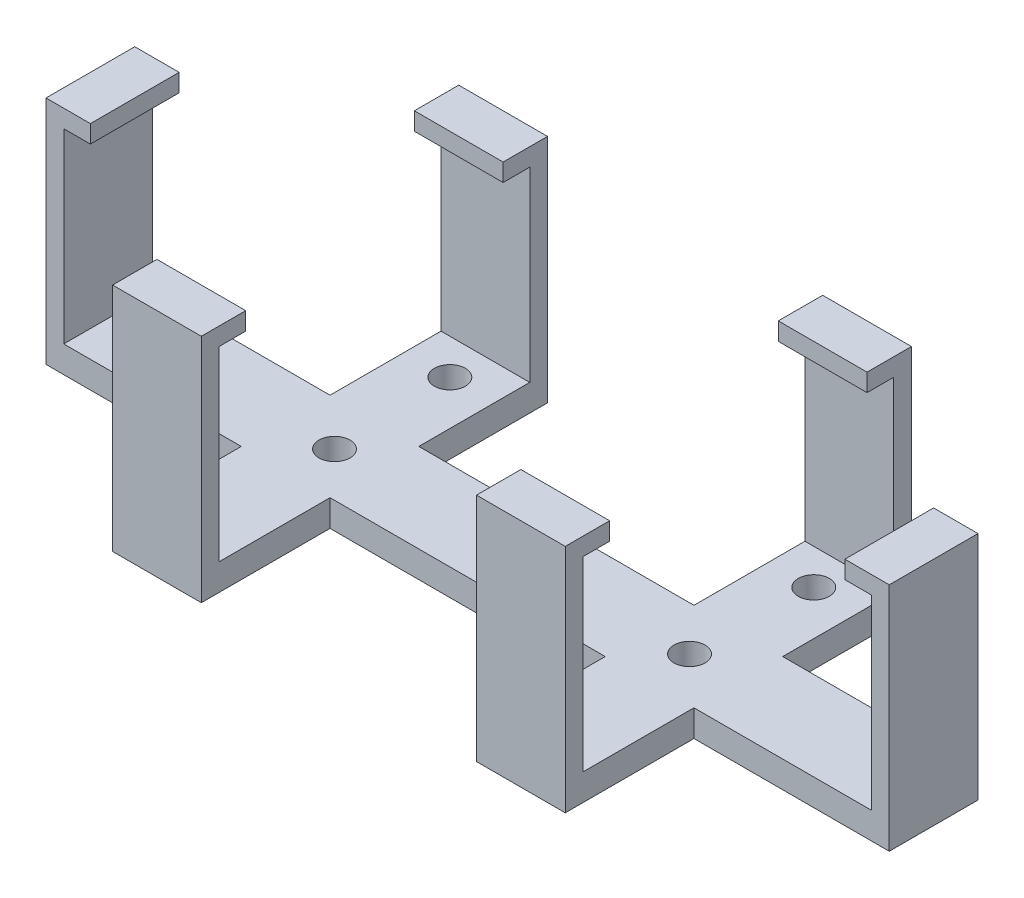
SolidWorks part; units mm, degrees
ref_plane "Front Plane" through (0, 0, 0) normal (0, 0, 1) x (1, 0, 0)
ref_plane "Top Plane" through (0, 0, 0) normal (0, 1, 0) x (1, 0, 0)
ref_plane "Right Plane" through (0, 0, 0) normal (1, 0, 0) x (0, 0, -1)
sketch "Sketch1" plane through (0, 0, 0) normal (0, 1, 0) x (1, 0, 0)
  line L1 (-35.1429, 16.9286) -> (55.8571, 16.9286)
  line L2 (-35.1429, 16.9286) -> (-35.1429, 6.9286)
  line L3 (-35.1429, 6.9286) -> (55.8571, 6.9286)
  line L4 (55.8571, 16.9286) -> (55.8571, 6.9286)
  line L5 (-15.1429, 16.9286) -> (-5.1429, 16.9286)
  line L6 (-15.1429, 16.9286) -> (-15.1429, 29.4286)
  line L7 (-15.1429, 29.4286) -> (-5.1429, 29.4286)
  line L8 (-5.1429, 16.9286) -> (-5.1429, 29.4286)
  line L9 (25.8571, 16.9286) -> (35.8571, 16.9286)
  line L10 (25.8571, 16.9286) -> (25.8571, 29.4286)
  line L11 (25.8571, 29.4286) -> (35.8571, 29.4286)
  line L12 (35.8571, 16.9286) -> (35.8571, 29.4286)
  line L13 (-15.1429, 6.9286) -> (-5.1429, 6.9286)
  line L14 (-15.1429, 6.9286) -> (-15.1429, -5.5714)
  line L15 (-15.1429, -5.5714) -> (-5.1429, -5.5714)
  line L16 (-5.1429, 6.9286) -> (-5.1429, -5.5714)
  line L17 (25.8571, 6.9286) -> (35.8571, 6.9286)
  line L18 (25.8571, 6.9286) -> (25.8571, -5.5714)
  line L19 (25.8571, -5.5714) -> (35.8571, -5.5714)
  line L20 (35.8571, 6.9286) -> (35.8571, -5.5714)
  line L21 (25.8571, 29.4286) -> (35.8571, 29.4286)
  line L22 (25.8571, 29.4286) -> (25.8571, 31.4286)
  line L23 (25.8571, 31.4286) -> (35.8571, 31.4286)
  line L24 (35.8571, 29.4286) -> (35.8571, 31.4286)
  line L25 (-15.1429, 29.4286) -> (-5.1429, 29.4286)
  line L26 (-15.1429, 29.4286) -> (-15.1429, 31.4286)
  line L27 (-15.1429, 31.4286) -> (-5.1429, 31.4286)
  line L28 (-5.1429, 29.4286) -> (-5.1429, 31.4286)
  line L29 (-15.1429, -5.5714) -> (-5.1429, -5.5714)
  line L30 (-15.1429, -5.5714) -> (-15.1429, -7.5714)
  line L31 (-15.1429, -7.5714) -> (-5.1429, -7.5714)
  line L32 (-5.1429, -5.5714) -> (-5.1429, -7.5714)
  line L33 (25.8571, -5.5714) -> (35.8571, -5.5714)
  line L34 (25.8571, -5.5714) -> (25.8571, -7.5714)
  line L35 (25.8571, -7.5714) -> (35.8571, -7.5714)
  line L36 (35.8571, -5.5714) -> (35.8571, -7.5714)
  line L37 (55.8571, 16.9286) -> (57.8571, 16.9286)
  line L38 (55.8571, 16.9286) -> (55.8571, 6.9286)
  line L39 (55.8571, 6.9286) -> (57.8571, 6.9286)
  line L40 (57.8571, 16.9286) -> (57.8571, 6.9286)
  line L41 (-35.1429, 16.9286) -> (-37.1429, 16.9286)
  line L42 (-35.1429, 16.9286) -> (-35.1429, 6.9286)
  line L43 (-35.1429, 6.9286) -> (-37.1429, 6.9286)
  line L44 (-37.1429, 16.9286) -> (-37.1429, 6.9286)
  circle A0 centre (-9.6429, 11.9286) radius 1.75
  circle A1 centre (30.3571, 11.9286) radius 1.75
  point P32 (-35.1429, 11.9286)
  point P33 (55.8571, 11.9286)
  dimension "D23" = 3.5
  dimension "D24" = 3.5
  dimension "D1" = 91
  dimension "D2" = 10
  dimension "D3" = 10
  dimension "D4" = 10
  dimension "D5" = 20
  dimension "D6" = 20
  dimension "D7" = 20
  dimension "D8" = 20
  dimension "D9" = 10
  dimension "D10" = 10
  dimension "D11" = 12.5
  dimension "D12" = 2
  dimension "D13" = 12.5
  dimension "D14" = 2
  dimension "D15" = 12.5
  dimension "D16" = 12.5
  dimension "D17" = 2
  dimension "D18" = 2
  dimension "D19" = 0
  dimension "D20" = 0
  dimension "D21" = 40
  dimension "D22" = 25.5
  dimension "D25" = 2
  dimension "D26" = 2
extrude "Boss-Extrude1" add sketch "Sketch1" along normal blind 3 contours L1 L8 L7 L6 | L4 L1 L2 L3 A1 A0 | L16 L3 L14 L15 | L20 L3 L18 L19 | L1 L12 L11 L10 region at (10.3571, 0, -11.9286) region at (-10.1429, 0, -23.1786) region at (-10.1429, 0, -0.6786) region at (30.8571, 0, -23.1786) region at (30.8571, 0, -0.6786)
extrude "Boss-Extrude2" add sketch "Sketch1<3>" along normal blind 24 contours L41 L44 L43 L2 | L32 L15 L30 L31 | L36 L19 L34 L35 | L40 L37 L4 L39 | L11 L24 L23 L22 | L7 L28 L27 L26 region at (-36.1429, 0, -11.9286) region at (-10.1429, 0, -30.4286) region at (-10.1429, 0, 6.5714) region at (30.8571, 0, -30.4286) region at (56.8571, 0, -11.9286) region at (30.8571, 0, 6.5714)
sketch "Sketch1<3>" plane through (0, 0, 0) normal (0, 1, 0) x (1, 0, 0) same geometry as "Sketch1"
sketch "Sketch2" plane through (0, 24, 0) normal (0, 1, 0) x (1, 0, 0)
  line L1 (-15.1429, 31.4286) -> (-5.1429, 31.4286)
  line L2 (-15.1429, 31.4286) -> (-15.1429, 26.4286)
  line L3 (-15.1429, 26.4286) -> (-5.1429, 26.4286)
  line L4 (-5.1429, 31.4286) -> (-5.1429, 26.4286)
  line L5 (25.8571, 31.4286) -> (35.8571, 31.4286)
  line L6 (25.8571, 31.4286) -> (25.8571, 26.4286)
  line L7 (25.8571, 26.4286) -> (35.8571, 26.4286)
  line L8 (35.8571, 31.4286) -> (35.8571, 26.4286)
  line L9 (57.8571, 16.9286) -> (52.8571, 16.9286)
  line L10 (57.8571, 16.9286) -> (57.8571, 6.9286)
  line L11 (57.8571, 6.9286) -> (52.8571, 6.9286)
  line L12 (52.8571, 16.9286) -> (52.8571, 6.9286)
  line L13 (35.8571, -7.5714) -> (25.8571, -7.5714)
  line L14 (35.8571, -7.5714) -> (35.8571, -2.5714)
  line L15 (35.8571, -2.5714) -> (25.8571, -2.5714)
  line L16 (25.8571, -7.5714) -> (25.8571, -2.5714)
  line L17 (-5.1429, -7.5714) -> (-15.1429, -7.5714)
  line L18 (-5.1429, -7.5714) -> (-5.1429, -2.5714)
  line L19 (-5.1429, -2.5714) -> (-15.1429, -2.5714)
  line L20 (-15.1429, -7.5714) -> (-15.1429, -2.5714)
  line L21 (-37.1429, 6.9286) -> (-32.1429, 6.9286)
  line L22 (-37.1429, 6.9286) -> (-37.1429, 16.9286)
  line L23 (-37.1429, 16.9286) -> (-32.1429, 16.9286)
  line L24 (-32.1429, 6.9286) -> (-32.1429, 16.9286)
  dimension "D1" = 10
  dimension "D2" = 5
  dimension "D3" = 5
  dimension "D4" = 10
  dimension "D5" = 10
  dimension "D6" = 5
  dimension "D7" = 5
  dimension "D8" = 10
  dimension "D9" = 10
  dimension "D10" = 5
  dimension "D11" = 5
  dimension "D12" = 10
extrude "Boss-Extrude3" add sketch "Sketch2" along normal blind 2
sketch "Sketch3" plane through (0, 0, 0) normal (0, -1, 0) x (1, 0, 0)
  line L0 (25.8571, -31.4286) -> (35.8571, -31.4286) construction
  line L1 (-15.1429, -31.4286) -> (-5.1429, -31.4286) construction
  line L2 (-5.1429, -16.9286) -> (-5.1429, -31.4286) construction
  line L3 (35.8571, -16.9286) -> (35.8571, -31.4286) construction
  circle A0 centre (-10.1429, -25.4286) radius 1.75
  circle A1 centre (30.8571, -25.4286) radius 1.75
  dimension "D5" = 3.5
  dimension "D6" = 3.5
  dimension "D1" = 6
  dimension "D2" = 6
  dimension "D3" = 5
  dimension "D4" = 5
extrude "Cut-Extrude1" cut sketch "Sketch3" against normal blind 12
